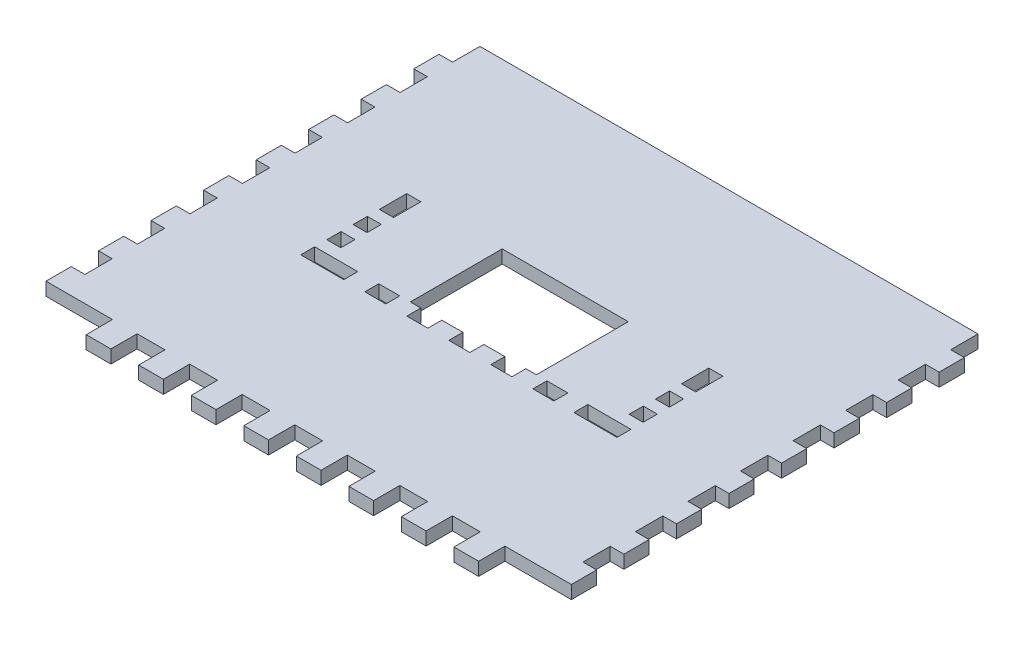
SolidWorks part; units mm, degrees
ref_plane "Front Plane" through (0, 0, 0) normal (0, 0, 1) x (1, 0, 0)
ref_plane "Top Plane" through (0, 0, 0) normal (0, 1, 0) x (1, 0, 0)
ref_plane "Right Plane" through (0, 0, 0) normal (1, 0, 0) x (0, 0, -1)
sketch "Sketch1" plane through (0, 0, 0) normal (0, 1, 0) x (1, 0, 0)
  line L1 (-63.5, -53.975) -> (63.5, -53.975)
  line L2 (-63.5, -53.975) -> (-63.5, 53.975)
  line L3 (-63.5, 53.975) -> (63.5, 53.975)
  line L4 (63.5, -53.975) -> (63.5, 53.975)
  line L5 (-63.5, -53.975) -> (63.5, 53.975) construction
  line L6 (-63.5, 53.975) -> (63.5, -53.975) construction
  point P0 (0, 0)
  dimension "D1" = 127
  dimension "D2" = 107.95
extrude "Boss-Extrude1" add sketch "Sketch1" along normal blind 3.175
sketch "Sketch2" plane through (0, 0, 0) normal (0, -1, 0) x (1, 0, 0)
  line L0 (-34.7345, 47.625) -> (-41.4655, 47.625)
  line L5 (63.5, 53.975) -> (63.5, -53.975) construction
  line L34 (0, 0) -> (0, -14.8721) construction
  line L39 (63.5, 41.529) -> (60.198, 41.529)
  line L41 (63.5, 54.229) -> (63.5, 47.625)
  line L42 (63.5, 47.625) -> (60.198, 47.625)
  line L44 (63.5, 41.529) -> (63.5, 34.925)
  line L45 (63.5, 34.925) -> (60.198, 34.925)
  line L46 (60.198, 41.529) -> (60.198, 34.925)
  line L47 (63.5, 28.829) -> (60.198, 28.829)
  line L48 (63.5, 28.829) -> (63.5, 22.225)
  line L49 (63.5, 22.225) -> (60.198, 22.225)
  line L50 (60.198, 28.829) -> (60.198, 22.225)
  line L51 (63.5, 16.129) -> (60.198, 16.129)
  line L52 (63.5, 16.129) -> (63.5, 9.525)
  line L53 (63.5, 9.525) -> (60.198, 9.525)
  line L54 (60.198, 16.129) -> (60.198, 9.525)
  line L55 (63.5, 3.429) -> (60.198, 3.429)
  line L56 (63.5, 3.429) -> (63.5, -3.175)
  line L57 (63.5, -3.175) -> (60.198, -3.175)
  line L58 (60.198, 3.429) -> (60.198, -3.175)
  line L59 (63.5, -9.271) -> (60.198, -9.271)
  line L60 (63.5, -9.271) -> (63.5, -15.875)
  line L61 (63.5, -15.875) -> (60.198, -15.875)
  line L62 (60.198, -9.271) -> (60.198, -15.875)
  line L63 (63.5, -21.971) -> (60.198, -21.971)
  line L64 (63.5, -21.971) -> (63.5, -28.575)
  line L65 (63.5, -28.575) -> (60.198, -28.575)
  line L66 (60.198, -21.971) -> (60.198, -28.575)
  line L67 (63.5, -34.671) -> (60.198, -34.671)
  line L68 (63.5, -34.671) -> (63.5, -41.275)
  line L69 (63.5, -41.275) -> (60.198, -41.275)
  line L70 (60.198, -34.671) -> (60.198, -41.275)
  line L71 (-60.198, -34.671) -> (-60.198, -41.275)
  line L72 (-63.5, -41.275) -> (-60.198, -41.275)
  line L73 (-63.5, -34.671) -> (-63.5, -41.275)
  line L74 (-63.5, -34.671) -> (-60.198, -34.671)
  line L75 (-60.198, -21.971) -> (-60.198, -28.575)
  line L76 (-63.5, -28.575) -> (-60.198, -28.575)
  line L77 (-63.5, -21.971) -> (-63.5, -28.575)
  line L78 (-63.5, -21.971) -> (-60.198, -21.971)
  line L79 (-60.198, -9.271) -> (-60.198, -15.875)
  line L80 (-63.5, -15.875) -> (-60.198, -15.875)
  line L81 (-63.5, -9.271) -> (-63.5, -15.875)
  line L82 (-63.5, -9.271) -> (-60.198, -9.271)
  line L83 (-60.198, 3.429) -> (-60.198, -3.175)
  line L84 (-63.5, -3.175) -> (-60.198, -3.175)
  line L85 (-63.5, 3.429) -> (-63.5, -3.175)
  line L86 (-63.5, 3.429) -> (-60.198, 3.429)
  line L87 (-60.198, 16.129) -> (-60.198, 9.525)
  line L88 (-63.5, 9.525) -> (-60.198, 9.525)
  line L89 (-63.5, 16.129) -> (-63.5, 9.525)
  line L90 (-63.5, 16.129) -> (-60.198, 16.129)
  line L91 (-60.198, 28.829) -> (-60.198, 22.225)
  line L92 (-63.5, 22.225) -> (-60.198, 22.225)
  line L93 (-63.5, 28.829) -> (-63.5, 22.225)
  line L94 (-63.5, 28.829) -> (-60.198, 28.829)
  line L95 (-60.198, 41.529) -> (-60.198, 34.925)
  line L96 (-63.5, 34.925) -> (-60.198, 34.925)
  line L97 (-63.5, 41.529) -> (-63.5, 34.925)
  line L99 (-63.5, 47.625) -> (-60.198, 47.625)
  line L100 (-63.5, 54.229) -> (-63.5, 47.625)
  line L102 (-63.5, 41.529) -> (-60.198, 41.529)
  line L103 (60.198, 47.625) -> (47.4345, 47.625)
  line L104 (34.7345, 47.625) -> (34.7345, 54.229)
  line L106 (34.7345, 54.229) -> (28.7655, 54.229)
  line L107 (28.7655, 54.229) -> (28.7655, 47.625)
  line L108 (28.7655, 47.625) -> (22.0345, 47.625)
  line L109 (22.0345, 47.625) -> (22.0345, 54.229)
  line L110 (22.0345, 54.229) -> (16.0655, 54.229)
  line L111 (16.0655, 54.229) -> (16.0655, 47.625)
  line L112 (16.0655, 47.625) -> (9.3345, 47.625)
  line L113 (9.3345, 47.625) -> (9.3345, 54.229)
  line L114 (9.3345, 54.229) -> (3.3655, 54.229)
  line L115 (3.3655, 54.229) -> (3.3655, 47.625)
  line L116 (3.3655, 47.625) -> (-3.3655, 47.625)
  line L117 (-3.3655, 47.625) -> (-3.3655, 54.229)
  line L118 (-3.3655, 54.229) -> (-9.3345, 54.229)
  line L119 (-9.3345, 54.229) -> (-9.3345, 47.625)
  line L120 (-9.3345, 47.625) -> (-16.0655, 47.625)
  line L121 (-16.0655, 47.625) -> (-16.0655, 54.229)
  line L122 (-16.0655, 54.229) -> (-22.0345, 54.229)
  line L123 (-22.0345, 54.229) -> (-22.0345, 47.625)
  line L124 (-22.0345, 47.625) -> (-28.7655, 47.625)
  line L125 (-28.7655, 47.625) -> (-28.7655, 54.229)
  line L126 (-28.7655, 54.229) -> (-34.7345, 54.229)
  line L127 (-34.7345, 54.229) -> (-34.7345, 47.625)
  line L137 (-63.5, 54.229) -> (-63.5, 63.0316)
  line L138 (63.5, -53.975) -> (-63.5, -53.975) construction
  line L139 (-63.5, 63.0316) -> (63.5, 63.0316)
  line L140 (63.5, 63.0316) -> (63.5, 54.229)
  line L141 (63.5, -47.371) -> (63.5, -53.975)
  line L142 (63.5, -53.975) -> (60.198, -53.975)
  line L143 (60.198, -53.975) -> (60.198, -47.371)
  line L144 (60.198, -47.371) -> (63.5, -47.371)
  line L145 (-60.198, -47.371) -> (-63.5, -47.371)
  line L146 (-60.198, -53.975) -> (-60.198, -47.371)
  line L147 (-63.5, -53.975) -> (-60.198, -53.975)
  line L148 (-63.5, -47.371) -> (-63.5, -53.975)
  line L149 (-63.5, -53.975) -> (-63.5, 53.975) construction
  line L150 (63.5, 53.975) -> (63.5, -53.975) construction
  line L151 (41.4655, 47.625) -> (41.4655, 54.229)
  line L152 (41.4655, 54.229) -> (47.4345, 54.229)
  line L153 (47.4345, 54.229) -> (47.4345, 47.625)
  line L154 (-41.4655, 47.625) -> (-41.4655, 54.229)
  line L155 (-41.4655, 54.229) -> (-47.4345, 54.229)
  line L156 (-47.4345, 54.229) -> (-47.4345, 47.625)
  line L157 (-47.4345, 47.625) -> (-60.198, 47.625)
  line L158 (41.4655, 47.625) -> (34.7345, 47.625)
  point P3 (0, 47.625)
  dimension "D2" = 6.604
  dimension "D3" = 5.969
  dimension "D6" = 6.731
  dimension "D8" = 3.302
  dimension "D9" = 9
extrude "Cut-Extrude1" cut sketch "Sketch2" against normal through all
sketch "Sketch3" plane through (0, 3.175, 0) normal (0, 1, 0) x (1, 0, 0)
  line L0 (0, 3.175) -> (0, -47.625) construction
  line L1 (-3.3655, -47.625) -> (3.3655, -47.625) construction
  line L2 (0, 53.975) -> (0, 3.175) construction
  line L3 (60.198, 53.975) -> (-60.198, 53.975) construction
  line L4 (-38.227, -1.5745) -> (-34.85, -1.5745)
  line L5 (-38.227, 14.3005) -> (-34.798, 14.3005)
  line L6 (-38.227, 14.3005) -> (-38.227, 7.6965)
  line L7 (-38.227, 7.6965) -> (-34.798, 7.6965)
  line L8 (-34.798, 14.3005) -> (-34.798, 7.6965)
  line L9 (-38.227, 4.7755) -> (-34.85, 4.7755)
  line L10 (-38.227, 4.7755) -> (-38.227, 1.3465)
  line L11 (-38.227, 1.3465) -> (-34.85, 1.3465)
  line L12 (-34.85, 4.7755) -> (-34.85, 1.3465)
  line L13 (-38.227, -1.5745) -> (-38.227, -5.0035)
  line L14 (-38.227, -5.0035) -> (-34.85, -5.0035)
  line L15 (-34.85, -1.5745) -> (-34.85, -5.0035)
  line L16 (-12.573, -7.9505) -> (-7.493, -7.9505)
  line L17 (-38.227, -7.9505) -> (-27.813, -7.9505)
  line L18 (-38.227, -7.9505) -> (-38.227, -11.3275)
  line L19 (-38.227, -11.3275) -> (-27.813, -11.3275)
  line L20 (-27.813, -7.9505) -> (-27.813, -11.3275)
  line L25 (-22.733, -7.9505) -> (-17.653, -7.9505)
  line L26 (-22.733, -7.9505) -> (-22.733, -11.3275)
  line L27 (-22.733, -11.3275) -> (-17.653, -11.3275)
  line L28 (-17.653, -7.9505) -> (-17.653, -11.3275)
  line L29 (-12.573, -7.9505) -> (-12.573, -11.3275)
  line L30 (-12.573, -11.3275) -> (-7.493, -11.3275)
  line L31 (-7.493, -7.9505) -> (-7.493, -11.3275)
  line L32 (-2.413, -7.9505) -> (2.667, -7.9505)
  line L33 (-2.413, -7.9505) -> (-2.413, -11.3275)
  line L34 (-2.413, -11.3275) -> (2.667, -11.3275)
  line L35 (2.667, -7.9505) -> (2.667, -11.3275)
  line L36 (7.747, -7.9505) -> (12.827, -7.9505)
  line L37 (7.747, -7.9505) -> (7.747, -11.3275)
  line L38 (7.747, -11.3275) -> (12.827, -11.3275)
  line L39 (12.827, -7.9505) -> (12.827, -11.3275)
  line L40 (17.907, -7.9505) -> (22.987, -7.9505)
  line L41 (17.907, -7.9505) -> (17.907, -11.3275)
  line L42 (17.907, -11.3275) -> (22.987, -11.3275)
  line L43 (22.987, -7.9505) -> (22.987, -11.3275)
  line L44 (27.813, -7.9505) -> (27.813, -11.3275)
  line L45 (38.227, -11.3275) -> (27.813, -11.3275)
  line L46 (38.227, -7.9505) -> (38.227, -11.3275)
  line L47 (38.227, -7.9505) -> (27.813, -7.9505)
  line L48 (34.85, -1.5745) -> (34.85, -5.0035)
  line L49 (38.227, -5.0035) -> (34.85, -5.0035)
  line L50 (38.227, -1.5745) -> (38.227, -5.0035)
  line L51 (34.85, 4.7755) -> (34.85, 1.3465)
  line L52 (38.227, 1.3465) -> (34.85, 1.3465)
  line L53 (38.227, 4.7755) -> (38.227, 1.3465)
  line L54 (38.227, 4.7755) -> (34.85, 4.7755)
  line L55 (34.798, 14.3005) -> (34.798, 7.6965)
  line L56 (38.227, 7.6965) -> (34.798, 7.6965)
  line L57 (38.227, 14.3005) -> (38.227, 7.6965)
  line L58 (38.227, 14.3005) -> (34.798, 14.3005)
  line L59 (38.227, -1.5745) -> (34.85, -1.5745)
  line L60 (-34.798, 14.3005) -> (0, 14.3005) construction
  line L61 (0, 3.175) -> (-20.6204, 3.175) construction
  line L62 (-20.6204, 14.3005) -> (-20.6204, 3.175) construction
  line L63 (-20.6204, 3.175) -> (-20.6204, -7.9505) construction
  circle A0 centre (0, 3.175) radius 1.27
  point P12 (-36.5125, 14.3005)
  point P17 (-38.227, 3.061)
  point P18 (-38.227, 10.9985)
  point P27 (-38.227, -3.289)
  point P28 (-38.227, -9.639)
  dimension "D1" = 2.54
  dimension "D2" = 6.604
  dimension "D3" = 3.429
  dimension "D4" = 36.5125
  dimension "D6" = 3.429
  dimension "D7" = 7.9375
  dimension "D9" = 6.35
  dimension "D10" = 10.414
  dimension "D11" = 5.08
  dimension "D12" = 10.16
  dimension "D13" = 3.377
  dimension "D14" = 2.921
  dimension "D15" = 5.08
  dimension "D17" = 3.377
  dimension "D18" = 5.08
  dimension "D8" = 2
  dimension "D16" = 5
extrude "Cut-Extrude2" cut sketch "Sketch3" against normal through all
sketch "Sketch4" plane through (0, 3.175, 0) normal (0, 1, 0) x (1, 0, 0)
  line L5 (-12.7, -3.175) -> (12.7, -3.175)
  line L6 (-12.7, -3.175) -> (-12.7, 9.525)
  line L7 (-12.7, 9.525) -> (12.7, 9.525)
  line L8 (12.7, -3.175) -> (12.7, 9.525)
  line L9 (-12.7, -3.175) -> (12.7, 9.525) construction
  line L10 (-12.7, 9.525) -> (12.7, -3.175) construction
  point P0 (0, 3.175)
  dimension "D1" = 25.4
  dimension "D2" = 12.7
extrude "Cut-Extrude3" cut sketch "Sketch4" against normal through all
sketch "Sketch5" plane through (0, 3.175, 0) normal (0, 1, 0) x (1, 0, 0)
  line L0 (2.667, -7.9505) -> (-2.413, -7.9505) construction
  line L1 (-15.113, 9.525) -> (15.367, 9.525)
  line L2 (-15.113, 9.525) -> (-15.113, -7.9505)
  line L3 (-15.113, -7.9505) -> (15.367, -7.9505)
  line L4 (15.367, 9.525) -> (15.367, -7.9505)
  line L7 (12.7, 9.525) -> (-12.7, 9.525) construction
  line L8 (-12.573, -7.9505) -> (-12.573, -11.3275) construction
  line L9 (12.827, -11.3275) -> (12.827, -7.9505) construction
  dimension "D1" = 2.54
  dimension "D2" = 2.54
extrude "Cut-Extrude4" cut sketch "Sketch5" against normal through all
sketch "Sketch6" plane through (0, 3.175, 0) normal (0, 1, 0) x (1, 0, 0)
  line L0 (15.367, -7.9505) -> (15.367, 9.525) construction
  line L1 (-15.113, -7.9505) -> (15.367, -7.9505)
  line L2 (-15.113, -7.9505) -> (-15.113, 14.2745)
  line L3 (-15.113, 14.2745) -> (15.367, 14.2745)
  line L4 (15.367, -7.9505) -> (15.367, 14.2745)
  dimension "D1" = 22.225
extrude "Cut-Extrude5" cut sketch "Sketch6" against normal through all
ref_plane "Plane1" through (0, 0, -3.162) normal (0, 0, -1) x (-1, 0, 0)
ref_plane "Plane2" through (0.127, 0, 0) normal (-1, 0, 0) x (0, 0, 1)
ref_axis "Axis1" through (0.127, -0.1588, -3.162) along (0, 1, 0)
